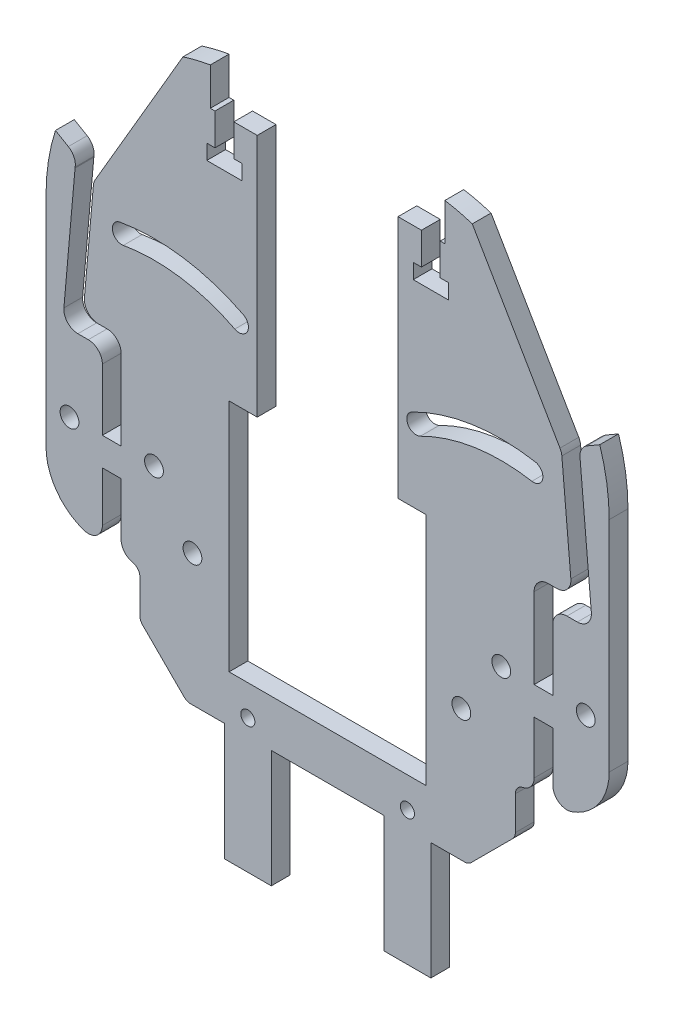
SolidWorks part; units mm, degrees
material "Pine"
ref_plane "Front Plane" through (0, 0, 0) normal (0, 0, 1) x (1, 0, 0)
ref_plane "Top Plane" through (0, 0, 0) normal (0, 1, 0) x (1, 0, 0)
ref_plane "Right Plane" through (0, 0, 0) normal (1, 0, 0) x (0, 0, -1)
sketch "Sketch1" plane through (0, 0, 0) normal (0, 0, 1) x (1, 0, 0)
  line L0 (0, 0) -> (0, -98.0129) construction
  line L1 (-40, 60) -> (-25, 60)
  line L2 (-40, 60) -> (-40, -60)
  line L3 (-40, -60) -> (-22, -60)
  line L4 (40, 60) -> (40, -60)
  line L5 (-40, 60) -> (40, -60) construction
  line L6 (-40, -60) -> (40, 60) construction
  line L7 (21, 0) -> (21, -50)
  line L8 (0, 0) -> (0, 75) construction
  line L9 (-21, -50) -> (21, -50)
  line L10 (15, 0) -> (15, 52)
  line L11 (-15, 0) -> (-15, 52)
  line L12 (-15, 0) -> (-15, 85.1588) construction
  line L13 (0, 0) -> (0, 85.1588) construction
  line L14 (15, 0) -> (15, 85.1588) construction
  line L15 (25, 60) -> (40, 60)
  line L16 (-15, 0) -> (-21, 0)
  line L17 (15, 0) -> (21, 0)
  line L18 (-21, 0) -> (-21, -50)
  line L19 (-12, -60) -> (12, -60)
  line L21 (-15, 52) -> (-25, 52)
  line L22 (-25, 60) -> (-25, 52)
  line L23 (22, -60) -> (22, -85)
  line L24 (22, -85) -> (12, -85)
  line L25 (15, 52) -> (25, 52)
  line L26 (25, 60) -> (25, 52)
  line L27 (12, -60) -> (12, -85)
  line L28 (22, -60) -> (40, -60)
  line L29 (-12, -60) -> (-12, -85)
  line L30 (-12, -85) -> (-22, -85)
  line L31 (-22, -60) -> (-22, -85)
  point P0 (0, 0)
  dimension "D1" = 120
  dimension "D2" = 80
  dimension "D3" = 50
  dimension "D4" = 8
  dimension "D5" = 110
  dimension "D8" = 8
  dimension "D9" = 50
  dimension "D10" = 25
  dimension "D11" = 42
  dimension "D12" = 25
  dimension "D13" = 10
  dimension "D14" = 24
  dimension "D15" = 12
  dimension "D6" = 15
  dimension "D7" = 15
extrude "Boss-Extrude1" add sketch "Sketch1" along normal blind 4
sketch "Sketch2" plane through (0, 0, 0) normal (0, 0, -1) x (-1, 0, 0)
  line L1 (-21, 0) -> (-21, -50) construction
  line L2 (40, -60) -> (22, -60) construction
  line L3 (28.8, -32) -> (28.8, 8.3751) construction
  line L4 (22, -85) -> (12, -85) construction
  line L5 (-12, -85) -> (-22, -85) construction
  line L6 (21, -50) -> (21, 0) construction
  line L7 (-28.5, -12) -> (-28.5, -69.2337) construction
  line L9 (40, -60) -> (22, -60) construction
  circle A0 centre (-28.5, -32) radius 2
  circle A1 centre (17, -56.5) radius 1.5
  circle A2 centre (28.8, -32) radius 2
  circle A3 centre (-17, -56.5) radius 1.5
  point P21 (17, -85)
  point P24 (-17, -85)
  dimension "D1" = 4
  dimension "D6" = 3
  dimension "D2" = 7.5
  dimension "D3" = 57.3
  dimension "D4" = 28
  dimension "D5" = 28
  dimension "D7" = 3.5
extrude "Cut-Extrude1" cut sketch "Sketch2" against normal through all
ref_plane "Plane1" through (0, 0, -2) normal (0, 0, 1) x (1, 0, 0)
sketch "Sketch4" plane through (0, 0, 4) normal (0, 0, 1) x (1, 0, 0)
  line L1 (-40, 60) -> (-60, 60)
  line L2 (-40, 60) -> (-40, -40)
  line L3 (-40, -40) -> (-60, -40)
  line L4 (-60, 60) -> (-60, -40)
  line L5 (40, 60) -> (60, 60)
  line L6 (40, 60) -> (40, -40)
  line L7 (40, -40) -> (60, -40)
  line L8 (60, 60) -> (60, -40)
  dimension "D1" = 20
  dimension "D2" = 20
  dimension "D3" = 100
  dimension "D4" = 100
extrude "Boss-Extrude2" add sketch "Sketch4" against normal blind 4
fillet "Fillet3" radius 42 2 edges at (60, 60, 2) (-60, 60, 2)
fillet "Fillet4" radius 12 2 edges at (60, -40, 2) (-60, -40, 2)
sketch "Sketch7" plane through (0, 0, 0) normal (0, 0, 1) x (1, 0, 0)
  line L1 (-60, 18.5874) -> (-60, -28) construction
  line L2 (60, -28) -> (60, 18.5874) construction
  line L3 (22, -60) -> (40, -60) construction
  line L4 (-40, -60) -> (-22, -60) construction
  circle A0 centre (-55, -20) radius 2
  circle A1 centre (55, -20) radius 2
  circle A2 centre (-37, -20) radius 2
  circle A3 centre (37, -20) radius 2
  point P10 (-60, -4.7063)
  dimension "D3" = 5
  dimension "D4" = 5
  dimension "D5" = 4
  dimension "D6" = 4
  dimension "D7" = 4
  dimension "D1" = 40
  dimension "D2" = 40
  dimension "D8" = 18
  dimension "D9" = 18
extrude "Cut-Extrude3" cut sketch "Sketch7" along normal through all
chamfer "Chamfer1" distance 10 angle 45 2 edges at (-40, -60, 2) (40, -60, 2)
fillet "Fillet8" radius 2 6 edges at (-30, -60, 2) (-40, -50, 2) (30, -60, 2) (40, -50, 2)
sketch "Sketch8" plane through (0, 0, 0) normal (0, 0, -1) x (-1, 0, 0)
  line L0 (0, 0) -> (0, 75) construction
  line L1 (0, 0) -> (0, 75)
  circle A0 centre (-37, -20) radius 40 construction
  arc A1 (-18.8713, 15.656) -> (-43.8713, 19.4054) centre (-37, -20) ccw construction
  arc A2 (-17.9648, 17.4388) -> (-44.2148, 21.3757) centre (-37, -20) ccw
  arc A3 (-19.7777, 13.8732) -> (-43.5277, 17.4351) centre (-37, -20) ccw
  arc A4 (-19.7777, 13.8732) -> (-17.9648, 17.4388) centre (-18.8713, 15.656) ccw
  arc A5 (-44.2148, 21.3757) -> (-43.5277, 17.4351) centre (-43.8713, 19.4054) ccw
  arc A6 (18.8713, 15.656) -> (43.8713, 19.4054) centre (37, -20) cw construction
  arc A7 (17.9648, 17.4388) -> (44.2148, 21.3757) centre (37, -20) cw
  arc A8 (19.7777, 13.8732) -> (43.5277, 17.4351) centre (37, -20) cw
  arc A9 (19.7777, 13.8732) -> (17.9648, 17.4388) centre (18.8713, 15.656) cw
  arc A10 (44.2148, 21.3757) -> (43.5277, 17.4351) centre (43.8713, 19.4054) cw
  point P5 (-31.0673, 19.5576)
  point P15 (31.0673, 19.5576)
  dimension "D1" = 80
  dimension "D2" = 2
  dimension "D3" = 25
extrude "Cut-Extrude4" cut sketch "Sketch8" against normal through all contours A7 A10 A8 A9 | A2 A5 A3 A4
sketch "Sketch9" plane through (0, 0, 4) normal (0, 0, 1) x (1, 0, 0)
  line L0 (-15, 52) -> (-25, 52) construction
  line L1 (-24, 52) -> (-20, 52)
  line L2 (-24, 52) -> (-24, 45.2)
  line L3 (-22, 40.3094) -> (-22, 51.6327) construction
  line L4 (-20, 52) -> (-20, 45.2)
  line L5 (-25, 52) -> (-25, 60) construction
  line L6 (-20, 45.2) -> (-18.25, 45.2)
  line L7 (-25.75, 45.2) -> (-24, 45.2)
  line L8 (-25.75, 45.2) -> (-25.75, 42)
  line L9 (-25.75, 42) -> (-18.25, 42)
  line L10 (-18.25, 45.2) -> (-18.25, 42)
  dimension "D1" = 3
  dimension "D2" = 2
  dimension "D3" = 2
  dimension "D4" = 7.5
  dimension "D5" = 3.2
  dimension "D6" = 10
  dimension "D7" = 3.75
extrude "Cut-Extrude5" cut sketch "Sketch9" against normal through all
mirror "Mirror1" about plane through (0, 0, 0) normal (1, 0, 0) of "Cut-Extrude5"
sketch "Sketch10" plane through (0, 0, 4) normal (0, 0, 1) x (1, 0, 0)
  line L0 (48, -40) -> (48, -3.7032)
  line L1 (48, -3.7032) -> (56.4853, -3.7032)
  line L2 (56.4853, -3.7032) -> (53.7624, 27.2115)
  line L3 (53.7624, 27.2115) -> (53.0064, 28.5068)
  line L4 (44, -40) -> (44, 0.2968)
  line L5 (44, 0.2968) -> (52.1175, 0.2968)
  line L6 (52.1175, 0.2968) -> (49.8564, 25.9687)
  line L7 (49.8564, 25.9687) -> (30.8242, 58.5817)
  line L8 (49.8564, 25.9687) -> (33.455, 54.0736) construction
  line L10 (50.9993, 12.9928) -> (55.0147, 12.9928)
  line L11 (44, -19.8516) -> (48, -19.8516)
  line L12 (44, -25.8516) -> (48, -25.8516)
  line L14 (51.5277, 6.9928) -> (55.5432, 6.9928)
  line L15 (44, -40) -> (48, -40)
  line L16 (50.9993, 6.9928) -> (55.0147, 6.9928) construction
  line L17 (53.0064, 28.5068) -> (57.9926, 31.4167)
  line L20 (53.7624, 27.2115) -> (36.9098, 56.0897) construction
  arc A0 (60, 18.5874) -> (25, 60) centre (18, 18.5874) ccw construction
  arc A1 (57.9926, 31.4167) -> (30.8242, 58.5817) centre (18, 18.5874) ccw
  arc A2 (60, 18.5874) -> (25, 60) centre (18, 18.5874) ccw construction
  dimension "D1" = 4
  dimension "D2" = 6
  dimension "D3" = 1.4998
  dimension "D4" = 32.613
  dimension "D5" = 14.1484
  dimension "D6" = 46.9928
  dimension "D7" = 154.767
  dimension "D8" = 30.9146
  dimension "D9" = 5.7731
extrude "Cut-Extrude6" cut sketch "Sketch10" against normal through all
mirror "Mirror5" about plane through (0, 0, 0) normal (1, 0, 0) of "Cut-Extrude6"
fillet "Fillet11" radius 3 16 edges at (-53.7624, 27.2115, 2) (-49.8564, 25.9687, 2) (-52.1175, 0.2968, 2) (-56.4853, -3.7032, 2) (-48, -3.7032, 2) (-44, 0.2968, 2) (-48, -40, 2) (-44, -40, 2) (53.7624, 27.2115, 2) (49.8564, 25.9687, 2) (52.1175, 0.2968, 2) (56.4853, -3.7032, 2) (48, -3.7032, 2) (44, 0.2968, 2) (44, -40, 2) (48, -40, 2)
fillet "Fillet12" radius 3 2 edges at (-53.0064, 28.5068, 2) (53.0064, 28.5068, 2)
